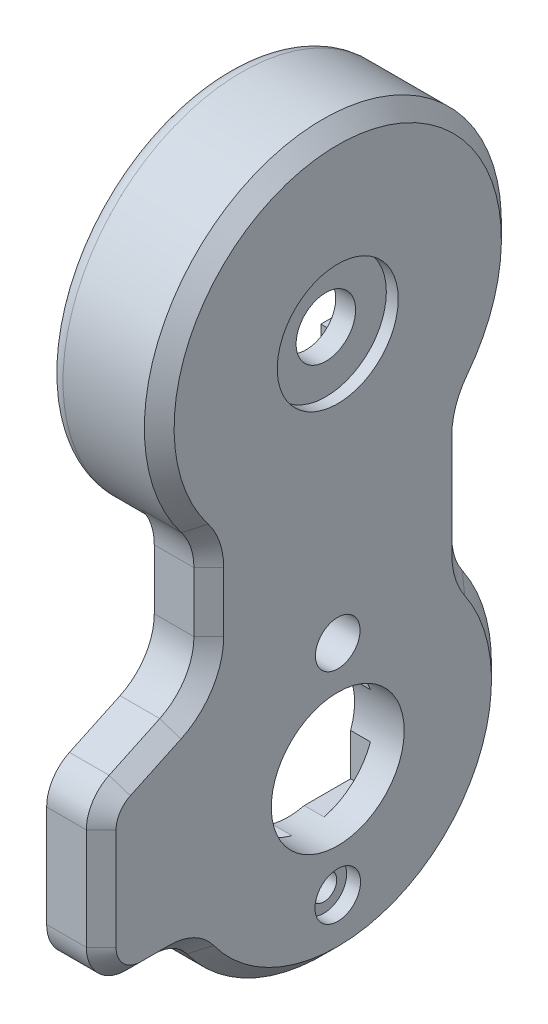
SolidWorks part; units mm, degrees
ref_plane "Front Plane" through (0, 0, 0) normal (0, 0, 1) x (1, 0, 0)
ref_plane "Top Plane" through (0, 0, 0) normal (0, 1, 0) x (1, 0, 0)
ref_plane "Right Plane" through (0, 0, 0) normal (1, 0, 0) x (0, 0, -1)
sketch "Sketch1" plane through (0, 0, 0) normal (1, 0, 0) x (0, 0, -1)
  line L0 (-53, 3.3371) -> (-53, -7.0385)
  line L1 (-82.9482, -28.4) -> (-85.85, -28.4)
  line L2 (-89.85, -24.4) -> (-89.85, -14.1397)
  line L3 (-87.5516, -10.5196) -> (-82.4476, -8.1205)
  line L4 (-79, -2.6905) -> (-79, 3.3371)
  arc A0 (-80.25, 7.0028) -> (-51.75, 7.0028) centre (-66, 18) cw
  arc A1 (-51.75, 7.0028) -> (-53, 3.3371) centre (-47, 3.3371) ccw
  arc A2 (-53, -7.0385) -> (-51.9565, -10.4198) centre (-47, -7.0385) ccw
  arc A3 (-51.9565, -10.4198) -> (-79.7199, -30.0381) centre (-66, -20) cw
  arc A4 (-79.7199, -30.0381) -> (-82.9482, -28.4) centre (-82.9482, -32.4) ccw
  arc A5 (-85.85, -28.4) -> (-89.85, -24.4) centre (-85.85, -24.4) cw
  arc A6 (-89.85, -14.1397) -> (-87.5516, -10.5196) centre (-85.85, -14.1397) cw
  arc A7 (-82.4476, -8.1205) -> (-79, -2.6905) centre (-85, -2.6905) ccw
  arc A8 (-79, 3.3371) -> (-80.25, 7.0028) centre (-85, 3.3371) ccw
extrude "Boss-Extrude1" add sketch "Sketch1" along normal blind 5.5 from offset 55.1
sketch "Sketch2" plane through (0, 0, 0) normal (1, 0, 0) x (0, 0, -1)
  line L0 (-53.8, 3.3371) -> (-53.8, -7.0385)
  line L1 (-82.9482, -27.6) -> (-85.85, -27.6)
  line L2 (-89.05, -24.4) -> (-89.05, -14.1397)
  line L3 (-87.2113, -11.2436) -> (-82.1073, -8.8446)
  line L4 (-78.2, -2.6905) -> (-78.2, 3.3371)
  arc A0 (-79.6167, 7.4916) -> (-52.3833, 7.4916) centre (-66, 18) cw
  arc A1 (-52.3833, 7.4916) -> (-53.8, 3.3371) centre (-47, 3.3371) ccw
  arc A2 (-53.8, -7.0385) -> (-52.6174, -10.8706) centre (-47, -7.0385) ccw
  arc A3 (-52.6174, -10.8706) -> (-79.0743, -29.5657) centre (-66, -20) cw
  arc A4 (-79.0743, -29.5657) -> (-82.9482, -27.6) centre (-82.9482, -32.4) ccw
  arc A5 (-85.85, -27.6) -> (-89.05, -24.4) centre (-85.85, -24.4) cw
  arc A6 (-89.05, -14.1397) -> (-87.2113, -11.2436) centre (-85.85, -14.1397) cw
  arc A7 (-82.1073, -8.8446) -> (-78.2, -2.6905) centre (-85, -2.6905) ccw
  arc A8 (-78.2, 3.3371) -> (-79.6167, 7.4916) centre (-85, 3.3371) ccw
extrude "Boss-Extrude2" add sketch "Sketch2" along normal blind 0.6 from offset 55 separate body
combine bodies "Combine1" operation type subtract main body 101 bodies to subtract 102
sketch "Sketch3" plane through (0, 0, 0) normal (1, 0, 0) x (0, 0, -1)
  circle A0 centre (-66, 18) radius 18
  circle A1 centre (-66, 18) radius 16.3
extrude "Boss-Extrude3" add sketch "Sketch3" along normal blind 6.2 from offset 49.4
chamfer "Chamfer1" distance 1.5 angle 45 14 edges at (60.6, -5.9065, 79.9347) (60.6, -9.3201, 84.9996) (60.6, 0.3233, 79) (60.6, -11.9956, 89.2269) (60.6, 5.2736, 79.3211) (60.6, -19.2698, 89.85) (60.6, 36, 66) (60.6, -27.2284, 88.6784) (60.6, 5.2736, 52.6789) (60.6, -28.4, 84.3991) (60.6, -1.8507, 53) (60.6, -28.833, 81.1381) (60.6, -8.8078, 52.7332) (60.6, -33.8836, 56.1895)
fillet "Fillet1" radius 1.5 1 edges at (49.4, 18, 48)
sketch "Sketch4" plane through (0, 0, 0) normal (0, 0, 1) x (1, 0, 0)
  line L1 (55.1, 6.5) -> (57.4, 6.5)
  line L2 (55.1, 6.5) -> (55.1, 29.5)
  line L3 (55.1, 29.5) -> (57.4, 29.5)
  line L4 (57.4, 6.5) -> (57.4, 29.5)
extrude "Boss-Extrude4" add sketch "Sketch4" along normal blind 6.6 from offset 62.7 separate body
combine bodies "Combine2" operation type subtract main body 104 bodies to subtract 105
sketch "Sketch5" plane through (0, 0, 0) normal (0, 0, 1) x (1, 0, 0)
  line L1 (55.1, 14.7) -> (57.4, 14.7)
  line L2 (55.1, 14.7) -> (55.1, 21.3)
  line L3 (55.1, 21.3) -> (57.4, 21.3)
  line L4 (57.4, 14.7) -> (57.4, 21.3)
extrude "Boss-Extrude5" add sketch "Sketch5" along normal blind 23 from offset 54.5 separate body
combine bodies "Combine3" operation type subtract main body 106 bodies to subtract 107
sketch "Sketch6" plane through (0, 0, 0) normal (1, 0, 0) x (0, 0, -1)
  circle A0 centre (-66, 18) radius 4.6
extrude "Boss-Extrude6" add sketch "Sketch6" along normal blind 2.3 from offset 55.1 separate body
combine bodies "Combine4" operation type subtract main body 108 bodies to subtract 109
sketch "Sketch7" plane through (0, 0, 0) normal (1, 0, 0) x (0, 0, -1)
  circle A0 centre (-66, 18) radius 6.1
extrude "Boss-Extrude7" add sketch "Sketch7" along normal blind 1.7 from offset 59.4 separate body
combine bodies "Combine5" operation type subtract main body 110 bodies to subtract 111
sketch "Sketch8" plane through (0, 0, 0) normal (1, 0, 0) x (0, 0, -1)
  circle A0 centre (-66, 18) radius 3
extrude "Boss-Extrude8" add sketch "Sketch8" along normal blind 2.2 from offset 57.3 separate body
combine bodies "Combine6" operation type subtract main body 112 bodies to subtract 113
sketch "Sketch9" plane through (0, 0, 0) normal (0, 0, 1) x (1, 0, 0)
  line L1 (57.3, 24.6) -> (59.6, 24.6)
  line L2 (57.3, 24.6) -> (57.3, 28)
  line L3 (57.3, 28) -> (59.6, 28)
  line L4 (59.6, 24.6) -> (59.6, 28)
extrude "Boss-Extrude9" add sketch "Sketch9" along normal blind 1.8 from offset 65.1 separate body
combine bodies "Combine7" operation type subtract main body 114 bodies to subtract 115
sketch "Sketch10" plane through (0, 0, 0) normal (0, 0, 1) x (1, 0, 0)
  line L1 (57.3, 17.1) -> (59.6, 17.1)
  line L2 (57.3, 17.1) -> (57.3, 18.9)
  line L3 (57.3, 18.9) -> (59.6, 18.9)
  line L4 (59.6, 17.1) -> (59.6, 18.9)
extrude "Boss-Extrude10" add sketch "Sketch10" along normal blind 3.4 from offset 72.6 separate body
combine bodies "Combine8" operation type subtract main body 116 bodies to subtract 117
sketch "Sketch11" plane through (0, 0, 0) normal (0, 0, 1) x (1, 0, 0)
  line L1 (57.3, 8) -> (59.6, 8)
  line L2 (57.3, 8) -> (57.3, 11.4)
  line L3 (57.3, 11.4) -> (59.6, 11.4)
  line L4 (59.6, 8) -> (59.6, 11.4)
extrude "Boss-Extrude11" add sketch "Sketch11" along normal blind 1.8 from offset 65.1 separate body
combine bodies "Combine9" operation type subtract main body 118 bodies to subtract 119
sketch "Sketch12" plane through (0, 0, 0) normal (0, 0, 1) x (1, 0, 0)
  line L1 (57.3, 17.1) -> (59.6, 17.1)
  line L2 (57.3, 17.1) -> (57.3, 18.9)
  line L3 (57.3, 18.9) -> (59.6, 18.9)
  line L4 (59.6, 17.1) -> (59.6, 18.9)
extrude "Boss-Extrude12" add sketch "Sketch12" along normal blind 3.4 from offset 56 separate body
combine bodies "Combine10" operation type subtract main body 120 bodies to subtract 121
sketch "Sketch13" plane through (0, 0, 0) normal (0, 0, 1) x (1, 0, 0)
  line L1 (49.3, -0.6) -> (55.6, -0.6)
  line L2 (49.3, -0.6) -> (49.3, 2.4984)
  line L3 (49.3, 2.4984) -> (55.6, 2.4984)
  line L4 (55.6, -0.6) -> (55.6, 2.4984)
extrude "Boss-Extrude13" add sketch "Sketch13" along normal blind 8 from offset 62 separate body
combine bodies "Combine11" operation type subtract main body 122 bodies to subtract 123
sketch "Sketch14" plane through (0, 0, 0) normal (0, 0, 1) x (1, 0, 0)
  line L1 (55.5, -21) -> (59.6, -21)
  line L2 (55.5, -21) -> (55.5, -19)
  line L3 (55.5, -19) -> (59.6, -19)
  line L4 (59.6, -21) -> (59.6, -19)
extrude "Boss-Extrude14" add sketch "Sketch14" along normal blind 2.9 from offset 55.875 separate body
combine bodies "Combine12" operation type subtract main body 124 bodies to subtract 125
sketch "Sketch15" plane through (0, 0, 0) normal (0, 0, 1) x (1, 0, 0)
  line L1 (55.5, -21) -> (59.6, -21)
  line L2 (55.5, -21) -> (55.5, -19)
  line L3 (55.5, -19) -> (59.6, -19)
  line L4 (59.6, -21) -> (59.6, -19)
extrude "Boss-Extrude15" add sketch "Sketch15" along normal blind 2.9 from offset 84.025 separate body
combine bodies "Combine13" operation type subtract main body 126 bodies to subtract 127
sketch "Sketch16" plane through (0, 0, 0) normal (0, 0, 1) x (1, 0, 0)
  line L1 (55.5, -26.5) -> (57.6, -26.5)
  line L2 (55.5, -26.5) -> (55.5, -13.5)
  line L3 (55.5, -13.5) -> (57.6, -13.5)
  line L4 (57.6, -26.5) -> (57.6, -13.5)
extrude "Boss-Extrude16" add sketch "Sketch16" along normal blind 23.4 from offset 59.7 separate body
combine bodies "Combine14" operation type subtract main body 128 bodies to subtract 129
sketch "Sketch17" plane through (0, 0, 0) normal (1, 0, 0) x (0, 0, -1)
  circle A0 centre (-66, -20) radius 6.7
extrude "Boss-Extrude17" add sketch "Sketch17" along normal blind 5.6 from offset 55.5 separate body
combine bodies "Combine15" operation type subtract main body 130 bodies to subtract 131
sketch "Sketch18" plane through (0, 0, 0) normal (1, 0, 0) x (0, 0, -1)
  circle A0 centre (-66, -9) radius 2.25
extrude "Boss-Extrude18" add sketch "Sketch18" along normal blind 5.6 from offset 55.5 separate body
combine bodies "Combine16" operation type subtract main body 132 bodies to subtract 133
sketch "Sketch19" plane through (0, 0, 0) normal (1, 0, 0) x (0, 0, -1)
  circle A0 centre (-66, -31) radius 2.3
extrude "Boss-Extrude19" add sketch "Sketch19" along normal blind 1.9 from offset 59.2 separate body
combine bodies "Combine17" operation type subtract main body 134 bodies to subtract 135
sketch "Sketch20" plane through (0, 0, 0) normal (1, 0, 0) x (0, 0, -1)
  circle A0 centre (-66, -31) radius 1.3
extrude "Boss-Extrude20" add sketch "Sketch20" along normal blind 3.75 from offset 55.5 separate body
combine bodies "Combine18" operation type subtract main body 136 bodies to subtract 137
sketch "Sketch21" plane through (0, 0, 0) normal (0, 0, 1) x (1, 0, 0)
  line L1 (55.5, -6.05) -> (58.6, -6.05)
  line L2 (55.5, -6.05) -> (55.5, -1.95)
  line L3 (55.5, -1.95) -> (58.6, -1.95)
  line L4 (58.6, -6.05) -> (58.6, -1.95)
extrude "Boss-Extrude21" add sketch "Sketch21" along normal blind 2.2 from offset 56.4 separate body
combine bodies "Combine19" operation type subtract main body 138 bodies to subtract 139
sketch "Sketch22" plane through (0, 0, 0) normal (0, 1, 0) x (1, 0, 0)
  line L0 (58.8, -58) -> (58.8, -57)
  line L1 (58.8, -57) -> (52.8, -57)
  line L2 (52.8, -57) -> (52.8, -56.6)
  line L3 (52.8, -56.6) -> (52.2, -56.6)
  line L4 (52.2, -56.6) -> (51.4, -57.4)
  line L5 (51.4, -57.4) -> (51.4, -58)
  line L6 (51.4, -58) -> (58.8, -58)
extrude "Boss-Extrude22" add sketch "Sketch22" along normal blind 3.5 from offset 5.75 offset against normal yes
sketch "Sketch23" plane through (0, 0, 0) normal (0, 0, 1) x (1, 0, 0)
  line L1 (55.5, -6.05) -> (58.6, -6.05)
  line L2 (55.5, -6.05) -> (55.5, -1.95)
  line L3 (55.5, -1.95) -> (58.6, -1.95)
  line L4 (58.6, -6.05) -> (58.6, -1.95)
extrude "Boss-Extrude23" add sketch "Sketch23" along normal blind 2.2 from offset 73.4 separate body
combine bodies "Combine20" operation type subtract main body 141 bodies to subtract 142
sketch "Sketch24" plane through (0, 0, 0) normal (0, 1, 0) x (1, 0, 0)
  line L0 (58.8, -74) -> (58.8, -75)
  line L1 (58.8, -75) -> (52.8, -75)
  line L2 (52.8, -75) -> (52.8, -75.4)
  line L3 (52.8, -75.4) -> (52.2, -75.4)
  line L4 (52.2, -75.4) -> (51.4, -74.6)
  line L5 (51.4, -74.6) -> (51.4, -74)
  line L6 (51.4, -74) -> (58.8, -74)
extrude "Boss-Extrude24" add sketch "Sketch24" along normal blind 3.5 from offset 5.75 offset against normal yes
